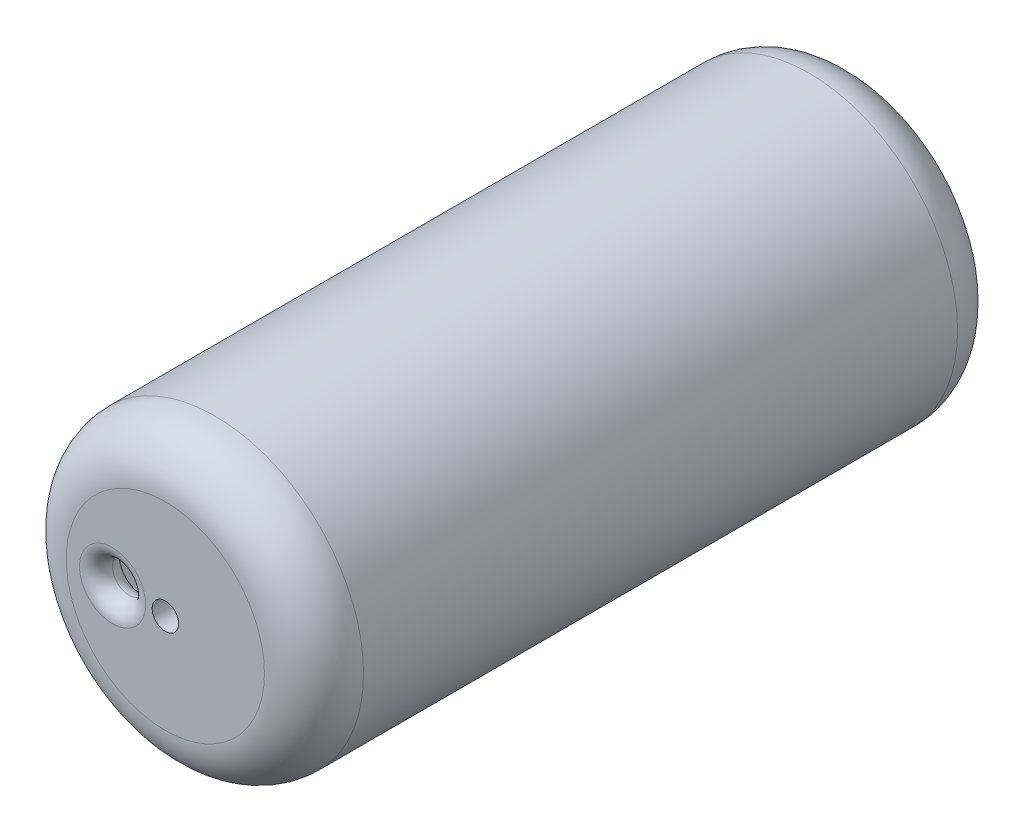
SolidWorks part; units mm, degrees
material "PET"
ref_plane "Front Plane" through (0, 0, 0) normal (0, 0, 1) x (1, 0, 0)
ref_plane "Top Plane" through (0, 0, 0) normal (0, 1, 0) x (1, 0, 0)
ref_plane "Right Plane" through (0, 0, 0) normal (1, 0, 0) x (0, 0, -1)
sketch "Sketch2" plane through (0, 0, 0) normal (0, 0, 1) x (1, 0, 0)
  circle A0 centre (0, 0) radius 14.2875
  dimension "D1" = 28.575
extrude "Boss-Extrude1" add sketch "Sketch2" along normal blind 3.175
sketch "Sketch3" plane through (0, 0, 3.175) normal (0, 0, 1) x (1, 0, 0)
  line L1 (-6.8453, -8.4963) -> (6.8453, -8.4963) construction
  line L2 (-6.8453, -8.4963) -> (-6.8453, 8.4963) construction
  line L3 (-6.8453, 8.4963) -> (6.8453, 8.4963) construction
  line L4 (6.8453, -8.4963) -> (6.8453, 8.4963) construction
  line L5 (-6.8453, -8.4963) -> (6.8453, 8.4963) construction
  line L6 (-6.8453, 8.4963) -> (6.8453, -8.4963) construction
  circle A0 centre (0, 0) radius 14.2875 construction
  circle A1 centre (0, 0) radius 14.2875
  circle A3 centre (0, 0) radius 11.7475
  dimension "D1" = 2.54
  dimension "D2" = 16.9926
  dimension "D3" = 13.6906
extrude "Boss-Extrude2" add sketch "Sketch3" along normal blind 60.2742
sketch "Sketch4" plane through (0, 0, 63.4492) normal (0, 0, 1) x (1, 0, 0)
  circle A1 centre (0, 0) radius 14.2875
  circle A2 centre (0, 0) radius 14.2875
  dimension "D1" = 0
extrude "Boss-Extrude3" add sketch "Sketch4" along normal blind 3.175
sketch "Sketch5" plane through (0, 0, 66.6242) normal (0, 0, 1) x (1, 0, 0)
  circle A0 centre (0, 0) radius 1.27
  circle A1 centre (-5.08, 0) radius 1.5875
  point P5 (0, 0)
  point P6 (0, 0)
  dimension "D1" = 2.54
  dimension "D2" = 3.175
  dimension "D3" = 5.08
extrude "Cut-Extrude1" cut sketch "Sketch5" against normal through all
fillet "Fillet1" radius 4.7625 2 edges at (14.2875, 0, 0) (14.2875, 0, 66.6242)
fillet "Fillet2" radius 1.5875 4 edges at (-3.4925, 0, 66.6242) (-3.4925, 0, 63.4492) (-3.4925, 0, 0) (-3.4925, 0, 3.175)
